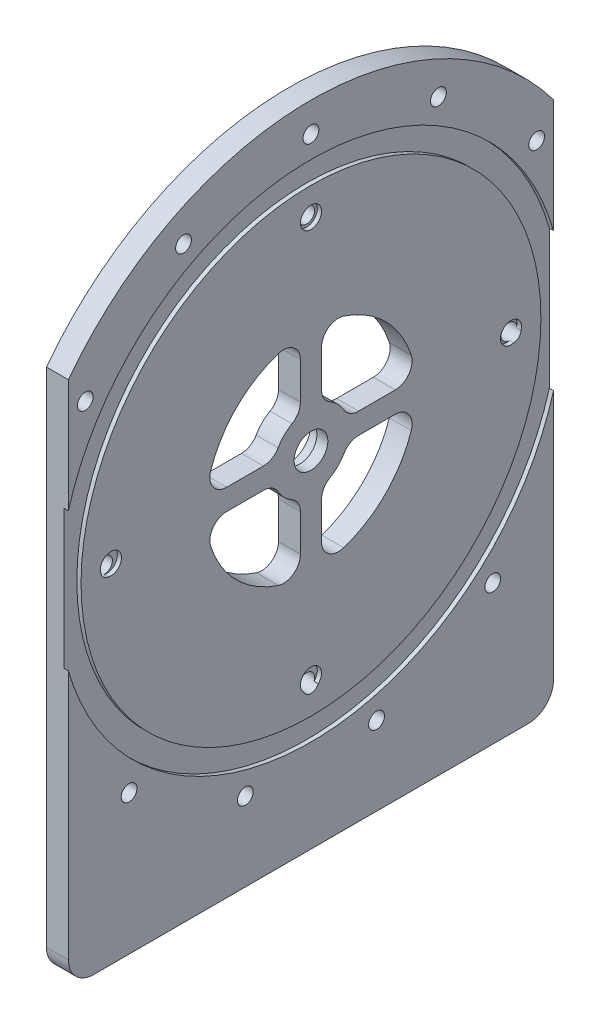
SolidWorks part; units mm, degrees
material "6061 Alloy"
ref_plane "Front Plane" through (0, 0, 0) normal (0, 0, 1) x (1, 0, 0)
ref_plane "Top Plane" through (0, 0, 0) normal (0, 1, 0) x (1, 0, 0)
ref_plane "Right Plane" through (0, 0, 0) normal (1, 0, 0) x (0, 0, -1)
sketch "Sketch1" plane through (0, 0, 0) normal (1, 0, 0) x (0, 0, -1)
  line L0 (0, -1000) -> (0, 49000) construction
  line L1 (5.5562, 0) -> (2.7781, 4.8119) construction
  line L2 (2.7781, 4.8119) -> (-2.7781, 4.8119) construction
  line L3 (-2.7781, 4.8119) -> (-5.5562, 0) construction
  line L4 (-5.5562, 0) -> (-2.7781, -4.8119) construction
  line L5 (-2.7781, -4.8119) -> (2.7781, -4.8119) construction
  line L6 (2.7781, -4.8119) -> (5.5562, 0) construction
  line L7 (-65.405, -103.8551) -> (65.405, -103.8551)
  line L8 (-73.025, -96.2351) -> (-73.025, -69.997)
  line L10 (73.025, -96.2351) -> (73.025, -69.997)
  circle A0 centre (0, 0) radius 69.85 construction
  circle A1 centre (0, 0) radius 76.2 construction
  circle A2 centre (0, 0) radius 5.08
  circle A3 centre (0, 0) radius 3.9688 construction
  arc A4 (79.6018, -44.9981) -> (-79.6018, -44.9981) centre (0, 0) ccw
  circle A5 centre (0, 0) radius 11.5094 construction
  circle A6 centre (0, 0) radius 91.44 construction
  arc A7 (65.405, -103.8551) -> (73.025, -96.2351) centre (65.405, -96.2351) ccw
  arc A8 (-65.405, -103.8551) -> (-73.025, -96.2351) centre (-65.405, -96.2351) cw
  arc A9 (79.6018, -44.9981) -> (73.025, -69.997) centre (123.825, -69.997) ccw
  arc A10 (-73.025, -69.997) -> (-79.6018, -44.9981) centre (-123.825, -69.997) ccw
  point P19 (73.025, -103.8551)
  point P26 (-73.025, -103.8551)
  dimension "D1" = 152.4
  dimension "D2" = 139.7
  dimension "D3" = 10.16
  dimension "D4" = 7.9375
  dimension "D5" = 15.24
  dimension "D6" = 23.0188
  dimension "D8" = 7.62
  dimension "D9" = 50.8
  dimension "D7" = 146.05
extrude "Boss-Extrude1" add sketch "Sketch1" along normal blind 6.604
sketch "Sketch2" plane through (0, 0, 0) normal (1, 0, 0) x (0, 0, -1)
  circle A0 centre (0, 0) radius 6.35 construction
  circle A1 centre (0, 0) radius 6.477
  dimension "D1" = 12.7
  dimension "D2" = 12.954
extrude "Cut-Extrude1" cut sketch "Sketch2" along direction (1, 0, 0) on the side of the normal blind 3.302
sketch "Sketch3" plane through (6.604, 0, 0) normal (1, 0, 0) x (0, 0, -1)
  circle A0 centre (0, 0) radius 75.946
  circle A1 centre (0, 0) radius 69.215
  dimension "D2" = 138.43
  dimension "D1" = 6.731
extrude "Cut-Extrude2" cut sketch "Sketch3" against normal blind 1.27
sketch "Sketch4" plane through (0, 0, 0) normal (-1, 0, 0) x (0, 0, 1)
  line L0 (0, -1000) -> (0, 49000) construction
  line L1 (-1000, 0) -> (49000, 0) construction
  circle A0 centre (-38.3629, 73.0944) radius 2.3813
  circle A1 centre (0, 82.55) radius 2.3812
  circle A3 centre (0, 0) radius 82.55 construction
  circle A4 centre (38.3629, 73.0944) radius 2.3813
  circle A5 centre (67.9373, 46.8937) radius 2.3812
  circle A6 centre (81.9481, 9.9503) radius 2.3813
  circle A7 centre (77.1856, -29.2726) radius 2.3813
  circle A8 centre (54.7408, -61.7896) radius 2.3812
  circle A9 centre (19.7555, -80.1512) radius 2.3813
  circle A10 centre (-19.7555, -80.1512) radius 2.3812
  circle A11 centre (-54.7408, -61.7896) radius 2.3812
  circle A12 centre (-77.1856, -29.2726) radius 2.3813
  circle A13 centre (-81.9481, 9.9503) radius 2.3812
  circle A14 centre (-67.9373, 46.8937) radius 2.3813
  point P34 (0, 0)
  dimension "D2" = 13
extrude "Cut-Extrude3" cut sketch "Sketch4" against normal through all
sketch "Sketch10" plane through (0, 0, 0) normal (-1, 0, 0) x (0, 0, 1)
  circle A0 centre (0, 0) radius 50.8
  circle A1 centre (0, 0) radius 57.15
extrude "Cut-Extrude6" cut sketch "Sketch10" against normal blind 1.27
sketch "Sketch12" plane through (0, 0, 0) normal (-1, 0, 0) x (0, 0, 1)
  circle A0 centre (0, 60.8743) radius 2.3813
  circle A1 centre (60.8743, 0) radius 2.3813
  circle A2 centre (0, -60.8743) radius 2.3813
  circle A3 centre (-60.8743, 0) radius 2.3813
  point P13 (0, 0)
  point P33 (0, 0)
  dimension "D1" = 4
extrude "Cut-Extrude7" cut sketch "Sketch12" against normal through all
sketch "Sketch15" plane through (6.604, 0, 0) normal (1, 0, 0) x (0, 0, -1)
  circle A0 centre (0, 60.8743) radius 3.175
  circle A1 centre (60.198, 0.6763) radius 3.175
  circle A2 centre (0, -59.5217) radius 3.175
  circle A3 centre (-60.198, 0.6763) radius 3.175
  point P12 (0, 0.6763)
  dimension "D1" = 4
  dimension "D2" = 60.198
extrude "Cut-Extrude11" cut sketch "Sketch15" against normal blind 1.27
sketch "Sketch16" plane through (0, 0, 0) normal (-1, 0, 0) x (0, 0, 1)
  line L0 (-73.025, -69.997) -> (-73.025, 55.0329)
  line L1 (-73.025, 55.0329) -> (-105.2318, 55.0329)
  line L2 (-105.2318, 55.0329) -> (-105.2318, -69.997)
  line L3 (-105.2318, -69.997) -> (-73.025, -69.997)
  line L4 (73.025, -69.997) -> (73.025, 55.0329)
  line L5 (73.025, 55.0329) -> (107.9275, 55.0329)
  line L6 (107.9275, 55.0329) -> (107.9275, -69.997)
  line L7 (107.9275, -69.997) -> (73.025, -69.997)
  arc A0 (79.6018, -44.9981) -> (-79.6018, -44.9981) centre (0, 0) ccw construction
extrude "Cut-Extrude12" cut sketch "Sketch16" against normal through all
sketch "Sketch18" plane through (0, 0, 0) normal (-1, 0, 0) x (0, 0, 1)
  line L0 (25.3603, 3.175) -> (14.2981, 3.175)
  line L1 (3.175, 25.3603) -> (3.175, 14.2981)
  line L2 (-3.175, 25.3603) -> (-3.175, 14.2981)
  line L3 (3.175, -25.3603) -> (3.175, -14.2981)
  line L4 (-25.3603, 3.175) -> (-14.2981, 3.175)
  line L5 (25.3603, -3.175) -> (14.2981, -3.175)
  line L7 (-25.3603, -3.175) -> (-14.2981, -3.175)
  line L8 (-3.175, -25.3603) -> (-3.175, -14.2981)
  line L14 (73.025, 55.0329) -> (73.025, -96.2351) construction
  arc A1 (-31.5909, -3.175) -> (3.175, 31.5909) centre (0, 0) ccw construction
  arc A2 (-10.9802, -3.175) -> (3.175, 10.9802) centre (0, 0) ccw construction
  arc A3 (-5.715, 9.8987) -> (-9.8987, 5.715) centre (0, 0) ccw
  arc A4 (-9.8274, 30.1908) -> (-30.1908, 9.8274) centre (0, 0) ccw
  arc A5 (-5.715, 9.8987) -> (-3.175, 14.2981) centre (-8.255, 14.2981) ccw
  arc A6 (-14.2981, 3.175) -> (-9.8987, 5.715) centre (-14.2981, 8.255) ccw
  arc A7 (-9.8274, 30.1908) -> (-3.175, 25.3603) centre (-8.255, 25.3603) cw
  arc A8 (-30.1908, 9.8274) -> (-25.3603, 3.175) centre (-25.3603, 8.255) ccw
  arc A9 (9.8987, 5.715) -> (5.715, 9.8987) centre (0, 0) ccw
  arc A10 (30.1908, 9.8274) -> (9.8274, 30.1908) centre (0, 0) ccw
  arc A11 (9.8987, 5.715) -> (14.2981, 3.175) centre (14.2981, 8.255) ccw
  arc A12 (3.175, 14.2981) -> (5.715, 9.8987) centre (8.255, 14.2981) ccw
  arc A13 (30.1908, 9.8274) -> (25.3603, 3.175) centre (25.3603, 8.255) cw
  arc A14 (9.8274, 30.1908) -> (3.175, 25.3603) centre (8.255, 25.3603) ccw
  arc A15 (5.715, -9.8987) -> (9.8987, -5.715) centre (0, 0) ccw
  arc A16 (9.8274, -30.1908) -> (30.1908, -9.8274) centre (0, 0) ccw
  arc A17 (5.715, -9.8987) -> (3.175, -14.2981) centre (8.255, -14.2981) ccw
  arc A18 (14.2981, -3.175) -> (9.8987, -5.715) centre (14.2981, -8.255) ccw
  arc A19 (9.8274, -30.1908) -> (3.175, -25.3603) centre (8.255, -25.3603) cw
  arc A20 (30.1908, -9.8274) -> (25.3603, -3.175) centre (25.3603, -8.255) ccw
  arc A21 (-9.8987, -5.715) -> (-5.715, -9.8987) centre (0, 0) ccw
  arc A22 (-30.1908, -9.8274) -> (-9.8274, -30.1908) centre (0, 0) ccw
  arc A23 (-9.8987, -5.715) -> (-14.2981, -3.175) centre (-14.2981, -8.255) ccw
  arc A24 (-3.175, -14.2981) -> (-5.715, -9.8987) centre (-8.255, -14.2981) ccw
  arc A25 (-30.1908, -9.8274) -> (-25.3603, -3.175) centre (-25.3603, -8.255) cw
  arc A26 (-9.8274, -30.1908) -> (-3.175, -25.3603) centre (-8.255, -25.3603) ccw
  circle A28 centre (0, 0) radius 6.35 construction
  circle A32 centre (0, 0) radius 6.477 construction
  point P56 (0.3033, -0.2194)
  point P71 (0.3033, -0.2194)
  point P72 (0, 0)
  dimension "D1" = 5.08
  dimension "D2" = 5.08
  dimension "D3" = 12.7
extrude "Cut-Extrude13" cut sketch "Sketch18" against normal through all
